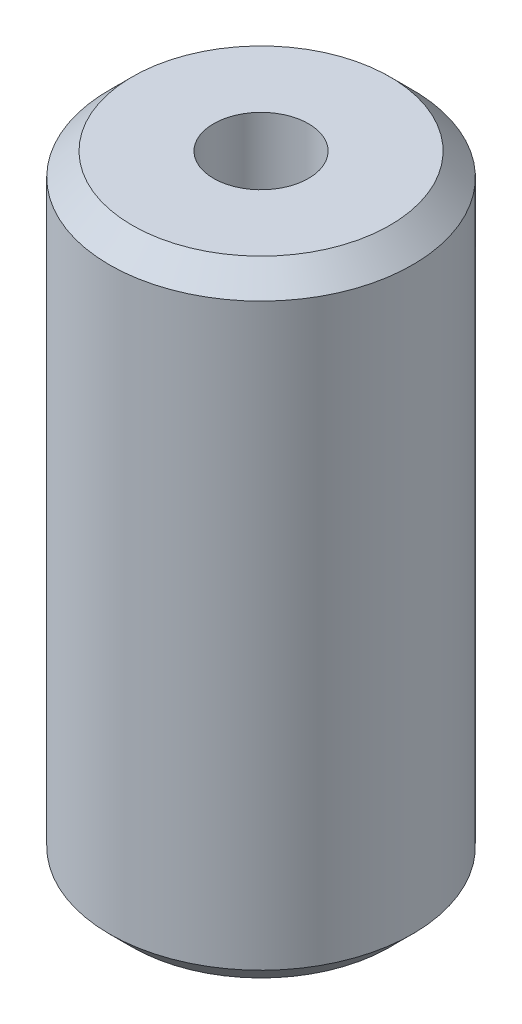
SolidWorks part; units mm, degrees
ref_plane "Front Plane" through (0, 0, 0) normal (0, 0, 1) x (1, 0, 0)
ref_plane "Top Plane" through (0, 0, 0) normal (0, 1, 0) x (1, 0, 0)
ref_plane "Right Plane" through (0, 0, 0) normal (1, 0, 0) x (0, 0, -1)
sketch "Sketch1" plane through (0, 0, 0) normal (0, 1, 0) x (1, 0, 0)
  circle A0 centre (0, 0) radius 10
  dimension "SHAFT_OD" = 20
extrude "Boss-Extrude1" add sketch "Sketch1" along normal blind 41.2454
sketch "Sketch2" plane through (0, 0, 0) normal (0, 1, 0) x (1, 0, 0)
  circle A0 centre (0, 0) radius 3.1308
  dimension "BORE_D" = 6.2617
extrude "Cut-Extrude1" cut sketch "Sketch2" along normal through all
chamfer "Chamfer1" distance 1.5047 angle 45 2 edges at (0, 41.2454, 10) (0, 0, 10)
